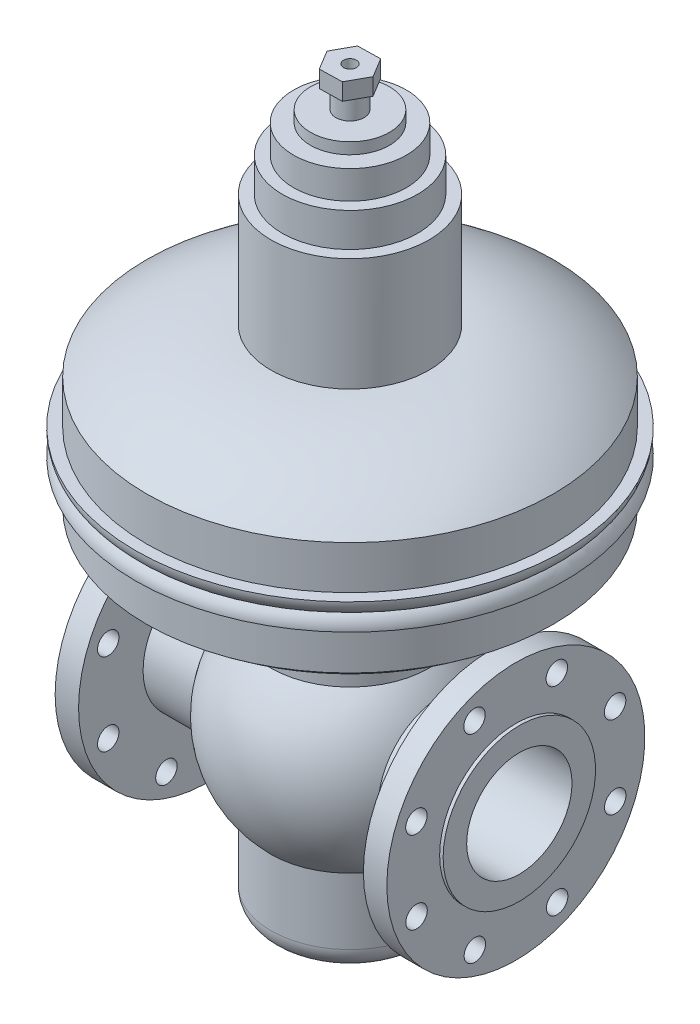
SolidWorks part; units mm, degrees
material "Cast Stainless Steel"
ref_plane "Front" through (0, 0, 0) normal (0, 0, 1) x (1, 0, 0)
ref_plane "Top" through (0, 0, 0) normal (0, 1, 0) x (1, 0, 0)
ref_plane "Right" through (0, 0, 0) normal (1, 0, 0) x (0, 0, -1)
other "Configuration Table"
sketch "Sketch1" plane through (0, 0, 0) normal (1, 0, 0) x (0, 0, -1)
  circle A0 centre (0, 0) radius 57.15
  dimension "D1" = 114.3
extrude "Base-Extrude" add sketch "Sketch1" along normal mid plane 300
sketch "Sketch2" plane through (0, 0, 0) normal (0, 1, 0) x (1, 0, 0)
  circle A0 centre (0, 0) radius 70
  dimension "D1" = 140
extrude "Boss-Extrude1" add sketch "Sketch2" along normal blind 400 and the other way blind 150
sketch "Sketch3" plane through (0, 0, 0) normal (0, 0, 1) x (1, 0, 0)
  line L0 (0, -115.863) -> (0, 215.6893) construction
  line L1 (0, 400) -> (0, -150) construction
  line L2 (0, -100) -> (0, 100)
  arc A0 (0, 100) -> (0, -100) centre (0, 0) cw
  dimension "D1" = 100
revolve "Boss-Revolve1" add sketch "Sketch3" angle 360 about L0
fillet "Fillet1" radius 20 1 edges at (0, -150, 70)
shell "Shell1" thickness 10.5 removed face at (150, 0, -57.15) removed face at (-150, 0, -57.15)
sketch "Sketch4" plane through (0, 0, 0) normal (0, 0, 1) x (1, 0, 0)
  line L0 (0, 0) -> (0, 349.2854) construction
  line L1 (0, 400) -> (0, 71.4143) construction
  line L2 (70, 210) -> (180, 210)
  line L3 (70, 71.4143) -> (70, 400) construction
  line L4 (180, 210) -> (180, 160)
  line L5 (70, 210) -> (70, 120)
  arc A0 (70, 120) -> (180, 160) centre (70, 291.25) ccw
  dimension "D1" = 180
  dimension "D2" = 90
  dimension "D3" = 50
  dimension "D4" = 210
revolve "Boss-Revolve2" add sketch "Sketch4" angle 360 about L0
sketch "Sketch5" plane through (0, 0, 0) normal (0, 0, 1) x (1, 0, 0)
  line L0 (190, 198.3801) -> (180, 198.3801)
  line L1 (180, 198.3801) -> (180, 210)
  line L2 (180, 210) -> (185, 210)
  line L3 (180, 210) -> (-180, 210) construction
  line L4 (180, 160) -> (180, 210) construction
  line L5 (0, 0) -> (0, 105.4969) construction
  line L6 (0, 120) -> (0, 71.4143) construction
  arc A0 (190, 198.3801) -> (185, 210) centre (173.9977, 198.3801) ccw
  dimension "D1" = 16.0023
  dimension "D2" = 10
  dimension "D3" = 5
revolve "Boss-Revolve3" add sketch "Sketch5" angle 360 about L5
mirror "Mirror1" about plane through (70, 210, 0) normal (0, -1, 0) of "Boss-Revolve2", "Boss-Revolve3"
sketch "Sketch6" plane through (0, 400, 0) normal (0, 1, 0) x (-1, 0, 0)
  circle A0 centre (0, 0) radius 60
  dimension "D1" = 120
extrude "Boss-Extrude2" add sketch "Sketch6" along normal blind 30
sketch "Sketch7" plane through (0, 430, 0) normal (0, 1, 0) x (-1, 0, 0)
  circle A0 centre (0, 0) radius 50
  dimension "D1" = 100
extrude "Boss-Extrude3" add sketch "Sketch7" along normal blind 25
sketch "Sketch8" plane through (0, 455, 0) normal (0, 1, 0) x (-1, 0, 0)
  circle A0 centre (0, 0) radius 35
  dimension "D1" = 70
extrude "Boss-Extrude4" add sketch "Sketch8" along normal blind 10
sketch "Sketch9" plane through (0, 465, 0) normal (0, 1, 0) x (-1, 0, 0)
  circle A0 centre (0, 0) radius 12.5
  dimension "D1" = 25
extrude "Boss-Extrude5" add sketch "Sketch9" along normal blind 35
sketch "hexagon2" plane through (-2.3581, 500, -8.0849) normal (0, 1, 0) x (-1, 0, 0)
  line L0 (17.6378, 8.4916) -> (7.2876, 25.6052)
  line L1 (7.2876, 25.6052) -> (-12.7082, 25.1985)
  line L2 (-12.7082, 25.1985) -> (-22.354, 7.6782)
  line L3 (-22.354, 7.6782) -> (-12.0038, -9.4354)
  line L4 (-12.0038, -9.4354) -> (7.9921, -9.0287)
  line L5 (7.9921, -9.0287) -> (17.6378, 8.4916)
  circle A0 centre (-2.3581, 8.0849) radius 20 construction
  dimension "Outside Diameter" = 40
extrude "Boss-Extrude6" add sketch "hexagon2" against normal blind 15
sketch "Sketch13" plane through (0, 0, 0) normal (0, 0, 1) x (1, 0, 0)
  line L0 (0, 0) -> (246.3426, 0) construction
  line L1 (150, 0) -> (82.0602, 0) construction
  line L2 (126.15, 57.15) -> (126.15, 114.3)
  line L3 (126.15, 114.3) -> (146.9, 114.3)
  line L4 (146.9, 114.3) -> (146.9, 67.5)
  line L5 (146.9, 67.5) -> (150, 67.5)
  line L6 (150, 67.5) -> (150, 57.15)
  line L7 (150, 57.15) -> (126.15, 57.15)
  line L8 (150, 57.15) -> (82.0602, 57.15) construction
  line L9 (150, -57.15) -> (150, 57.15) construction
  dimension "D1" = 114.3
  dimension "D2" = 67.5
  dimension "D3" = 20.75
  dimension "D4" = 3.1
revolve "Boss-Revolve4" add sketch "Sketch13" angle 360 about L0
mirror "Mirror2" about plane through (0, 0, 0) normal (1, 0, 0) of "Boss-Revolve4"
sketch "Sketch14" plane through (146.9, 0, 0) normal (1, 0, 0) x (0, 0, -1)
  line L1 (0, 0) -> (0, 114.3) construction
  line L2 (0, 0) -> (-36.6041, 87.9358) construction
  circle A0 centre (-36.6041, 87.9358) radius 9.5
  circle A1 centre (0, 0) radius 114.3 construction
  dimension "D1" = 19
  dimension "D2" = 95.25
  dimension "D3" = 22.6
extrude "Cut-Extrude1" cut sketch "Sketch14" against normal up to next
pattern_circular "CirPattern1" count 8 over 360 about axis through (0, 0, 0) along (1, 0, 0) of "Cut-Extrude1"
sketch "Sketch15" plane through (-146.9, 0, 0) normal (-1, 0, 0) x (0, 0, 1)
  line L0 (0, 0) -> (0, 62.7443) construction
  line L1 (0, 0) -> (-36.4506, 87.9995) construction
  circle A1 centre (-36.4506, 87.9995) radius 9.5
  circle A2 centre (0, 0) radius 95.25 construction
  dimension "D1" = 19
  dimension "D2" = 190.5
  dimension "D3" = 22.5
extrude "Cut-Extrude2" cut sketch "Sketch15" against normal up to next
pattern_circular "CirPattern2" count 8 over 360 about axis through (150, 0, 0) along (-1, 0, 0) of "Cut-Extrude2"
hole_wizard "1/2-20 Tapped Hole1" positions "Sketch17" profile "Sketch16" tap size "1/2-20" standard "Ansi Inch"
sketch "Sketch17" plane through (0, 500, 0) normal (0, 1, 0) x (-1, 0, 0)
  line L2 (-9.6457, -17.5203) -> (9.6457, 17.5203) construction
  line L4 (-19.9959, -0.4067) -> (19.9959, 0.4067) construction
  point P0 (0, 0)
sketch "Sketch16" plane through (0, 500, 0) normal (1, 0, 0) x (0, 0, 1)
  line L0 (0, 0) -> (0, 35.2076)
  line L1 (0, 35.2076) -> (5.7544, 31.75)
  line L2 (5.7544, 31.75) -> (5.7544, 0)
  line L5 (5.7544, 0) -> (0, 0)
  line L10 (0, 35.2076) -> (-5.7544, 31.75) construction
  line L11 (0, -6.35) -> (0, 107.95) construction
  dimension "Tap Drill Dia." = 11.5087
  dimension "Tap Drill Depth" = 31.75
  dimension "Drill Angle" = 118
cosmetic thread "Hole Thread1" parameters "D1"=25.4, "D2"=12.7
